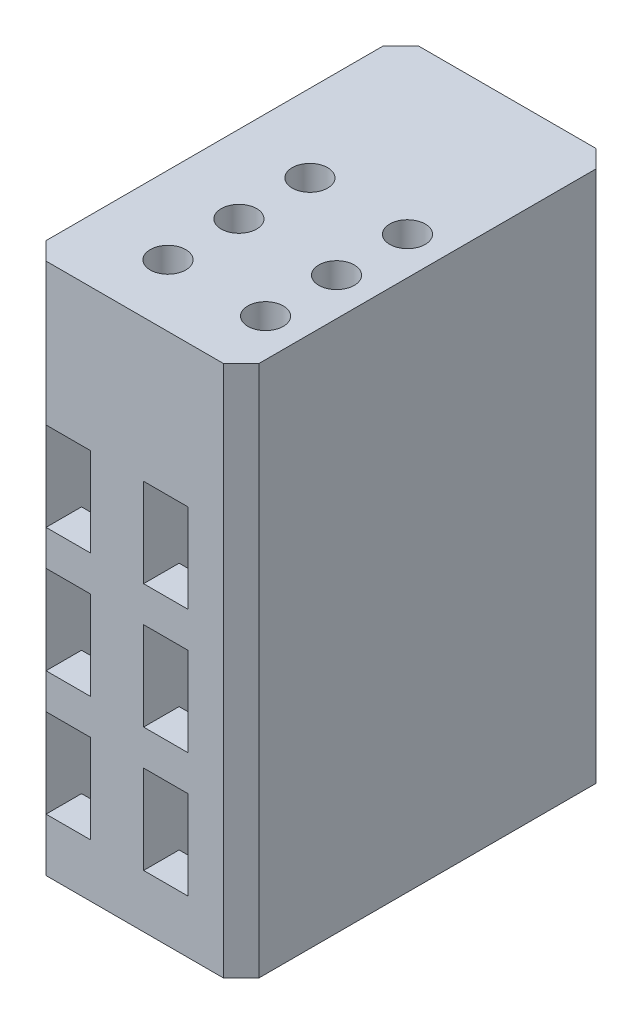
SolidWorks part; units mm, degrees
ref_plane "Спереди" through (0, 0, 0) normal (0, 0, 1) x (1, 0, 0)
ref_plane "Сверху" through (0, 0, 0) normal (0, 1, 0) x (1, 0, 0)
ref_plane "Справа" through (0, 0, 0) normal (1, 0, 0) x (0, 0, -1)
sketch "Эскиз1" plane through (0, 0, 0) normal (0, 1, 0) x (1, 0, 0)
  line L0 (0, 0) -> (0, 20) construction
  line L1 (5, 0) -> (-5, 0)
  line L2 (-5, 0) -> (-6, 1)
  line L3 (-6, 1) -> (-6, 10.5)
  line L4 (-5, 0) -> (-6, 0) construction
  line L5 (-6, 0) -> (-6, 1) construction
  line L6 (-6, 10.5) -> (-5, 10.5) construction
  line L7 (-5, 10.5) -> (-5, 2)
  line L8 (-5, 2) -> (-0.5, 2)
  line L9 (0, 2.0136) -> (0, 0) construction
  line L10 (-0.5, 2) -> (-0.5, 10.5)
  line L11 (-0.5, 2) -> (0, 2) construction
  line L12 (0.5, 2) -> (0.5, 10.5)
  line L13 (5, 10.5) -> (5, 2)
  line L14 (5, 2) -> (0.5, 2)
  line L15 (5, 0) -> (6, 1)
  line L16 (6, 1) -> (6, 10.5)
  line L17 (-6, 10.5) -> (-5, 10.5)
  line L18 (-0.5, 10.5) -> (0.5, 10.5)
  line L19 (5, 10.5) -> (6, 10.5)
  line L20 (-2.75, 2) -> (-2.75, 0) construction
  dimension "D1" = 20
  dimension "D2" = 1
  dimension "D3" = 1
  dimension "D4" = 5
  dimension "D5" = 9.5
  dimension "D6" = 1
  dimension "D7" = 2
  dimension "D8" = 0.5
  dimension "D9" = 8.5
extrude "Бобышка-Вытянуть1" add sketch "Эскиз1" along normal blind 30
mirror "Зеркальное отражение1" about plane through (-0.5, 30, -10.5) normal (0, 0, 1) of "Бобышка-Вытянуть1"
sketch "Эскиз2" plane through (0, 30, 0) normal (0, 1, 0) x (1, 0, 0)
  line L0 (-2.75, 2) -> (-0.5, 2) construction
  line L1 (-0.5, 2) -> (-5, 2) construction
  line L2 (-1.625, 2) -> (-1.625, 3.5) construction
  line L4 (-1.625, 3.5) -> (-1.625, 7.5) construction
  line L5 (-1.625, 7.5) -> (-1.625, 11.5) construction
  line L6 (-1.625, 11.5) -> (-1.625, 19) construction
  line L7 (-0.5, 19) -> (-5, 19) construction
  line L8 (-5, 2) -> (-0.5, 2)
  line L9 (-5, 2) -> (-5, 19)
  line L10 (-5, 19) -> (-0.5, 19)
  line L11 (-0.5, 2) -> (-0.5, 19)
  circle A1 centre (-1.625, 11.5) radius 1
  circle A2 centre (-1.625, 7.5) radius 1
  circle A3 centre (-1.625, 3.5) radius 1
  dimension "D4" = 2
  dimension "D1" = 7.5
  dimension "D2" = 4
  dimension "D3" = 4
  dimension "D5" = 3
extrude "Бобышка-Вытянуть2" add sketch "Эскиз2" against normal blind 3
sketch "Эскиз3" plane through (0, 27, 0) normal (0, -1, 0) x (1, 0, 0)
  line L0 (-0.5, -2) -> (-5, -2) construction
  line L1 (-0.5, -19) -> (-2.5, -19)
  line L2 (-0.5, -19) -> (-0.5, -2)
  line L3 (-0.5, -2) -> (-2.5, -2)
  line L4 (-2.5, -19) -> (-2.5, -13)
  line L5 (-1.625, -3.5) -> (-0.5, -3.5) construction
  line L6 (-1.625, -7.5) -> (-1.625, -6) construction
  line L8 (-0.5, -3.5) -> (-0.5, -5)
  line L9 (-0.5, -5) -> (-2.5, -5)
  line L11 (-1.625, -6) -> (-0.5, -6)
  line L12 (-1.625, -6) -> (-2.5, -6)
  line L13 (-1.625, -7.5) -> (-1.625, -9) construction
  line L14 (-1.625, -9) -> (-2.5, -9)
  line L15 (-1.625, -9) -> (-0.5, -9)
  line L16 (-2.5, -6) -> (-2.5, -5)
  line L17 (-1.625, -11.5) -> (-1.625, -10) construction
  line L18 (-1.625, -10) -> (-0.5, -10)
  line L19 (-1.625, -10) -> (-2.5, -10)
  line L20 (-1.625, -11.5) -> (-1.625, -13) construction
  line L21 (-1.625, -13) -> (-0.5, -13)
  line L22 (-1.625, -13) -> (-2.5, -13)
  line L23 (-2.5, -10) -> (-2.5, -9)
  line M16 (-0.5, -19) -> (-0.5, -2)
  line M19 (-5, -19) -> (-0.5, -19)
  dimension "D1" = 2
  dimension "D2" = 1.5
  dimension "D3" = 1.5
  dimension "D4" = 1.5
  dimension "D5" = 1.5
extrude "Бобышка-Вытянуть3" add sketch "Эскиз3" along normal blind 27 contours L21 L22 L4 M19 M16 | L23 L19 L18 L2 L15 L14 | L16 L12 L11 L2 L9 region at (-1.5, 27, -5.5) region at (-1.5, 27, -9.5) region at (-1.5, 27, -16)
pattern_linear "Линейный массив1" count 2 spacing 5.5 along (1, 0, 0) of "Бобышка-Вытянуть2"
pattern_linear "Линейный массив2" count 2 spacing 5.5 along (1, 0, 0) of "Бобышка-Вытянуть3"
sketch "Эскиз5" plane through (0, 0, -21) normal (0, 0, -1) x (-1, 0, 0)
  line L0 (5, 30) -> (5, 20) construction
  line L1 (5, 30) -> (5, 0) construction
  line L3 (5, 20) -> (2.5, 20)
  line L4 (5, 20) -> (5, 17)
  line L5 (5, 17) -> (2.5, 17)
  line L6 (2.5, 20) -> (2.5, 17)
  dimension "D1" = 10
  dimension "D2" = 2.5
  dimension "D3" = 3
extrude "Вырез-Вытянуть1" cut sketch "Эскиз5" against normal up to next contours L3 L6 L5 L4
pattern_linear "Линейный массив3" count 3 spacing 7 along (0, -1, 0) of "Вырез-Вытянуть1"
pattern_linear "Линейный массив4" count 2 spacing 5.5 along (1, 0, 0) of "Линейный массив3"
sketch "Эскиз6" plane through (0, 0, 0) normal (0, 0, 1) x (1, 0, 0)
  line L0 (-5, 30) -> (-5, 22) construction
  line L1 (-5, 30) -> (-5, 0) construction
  line L3 (-5, 22) -> (-2.5, 22)
  line L4 (-5, 22) -> (-5, 17)
  line L5 (-5, 17) -> (-2.5, 17)
  line L6 (-2.5, 22) -> (-2.5, 17)
  dimension "D1" = 8
  dimension "D2" = 5
  dimension "D3" = 2.5
extrude "Вырез-Вытянуть2" cut sketch "Эскиз6" against normal up to next
pattern_linear "Линейный массив5" count 3 spacing 7 along (0, -1, 0) of "Вырез-Вытянуть2"
pattern_linear "Линейный массив7" count 2 spacing 5.5 along (1, 0, 0) of "Линейный массив5"
